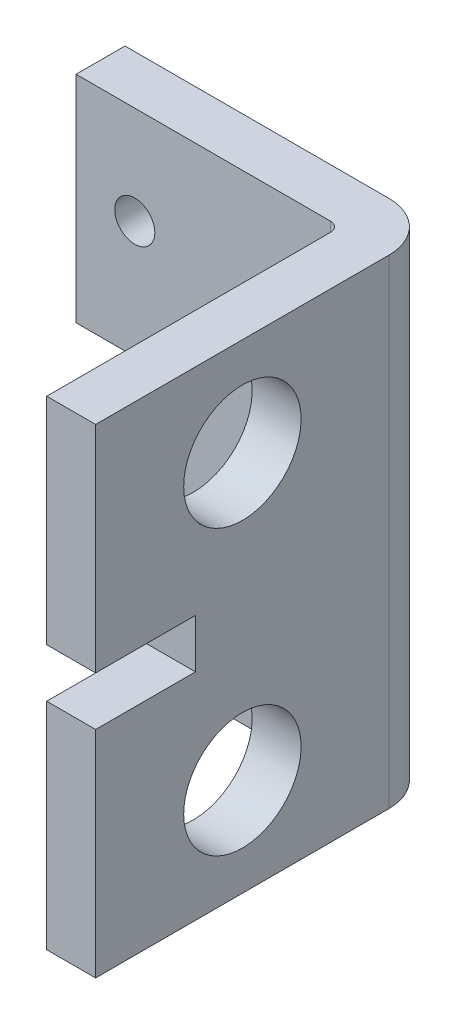
SolidWorks part; units mm, degrees
ref_plane "Front Plane" through (0, 0, 0) normal (0, 0, 1) x (1, 0, 0)
ref_plane "Top Plane" through (0, 0, 0) normal (0, 1, 0) x (1, 0, 0)
ref_plane "Right Plane" through (0, 0, 0) normal (1, 0, 0) x (0, 0, -1)
sketch "Sketch2" plane through (0, 0, 0) normal (0, 0, 1) x (1, 0, 0)
  line L1 (0, 0) -> (27, 0)
  line L2 (0, 0) -> (0, 49)
  line L3 (0, 49) -> (27, 49)
  line L4 (27, 0) -> (27, 49)
  line L5 (6, 39) -> (21, 39) construction
  line L6 (6, 39) -> (6, 10) construction
  line L7 (6, 10) -> (21, 10) construction
  line L8 (21, 39) -> (21, 10) construction
  circle A0 centre (6, 39) radius 2.05
  circle A1 centre (21, 39) radius 2.05
  circle A2 centre (6, 10) radius 2.05
  circle A3 centre (21, 10) radius 2.05
  point P13 (13.5, 10)
  point P14 (13.5, 0)
  point P15 (6, 24.5)
  point P16 (0, 24.5)
  dimension "D1" = 4.1
  dimension "D2" = 15
  dimension "D3" = 29
  dimension "D4" = 10
  dimension "D5" = 6
extrude "Boss-Extrude1" add sketch "Sketch2" along normal blind 5
sketch "Sketch4" plane through (0, 49, 0) normal (0, 1, 0) x (1, 0, 0)
  line L0 (27, 0) -> (0, 0) construction
  line L2 (32, -5) -> (32, -35)
  line L3 (32, -35) -> (27, -35)
  line L5 (27, -5) -> (27, 0) construction
  line L8 (27, -35) -> (27, 0)
  arc A0 (27, 0) -> (32, -5) centre (27, -5) cw
  dimension "D1" = 30
extrude "Boss-Extrude2" add sketch "Sketch4" against normal up to surface (49 mm away) up to face at (13.5, 0, 2.5)
sketch "Sketch5" plane through (27, 0, 0) normal (-1, 0, 0) x (0, 0, 1)
  line L1 (35, 0) -> (5, 0) construction
  line L2 (35, 0) -> (35, 49) construction
  circle A0 centre (20, 39) radius 6
  circle A1 centre (20, 10) radius 6
  point P4 (0, 0)
  point P5 (0, 0)
  dimension "D1" = 12
  dimension "D2" = 29
  dimension "D3" = 10
  dimension "D4" = 15
extrude "Cut-Extrude1" cut sketch "Sketch5" against normal through all
fillet "Fillet1" radius 1 1 edges at (27, 24.5, 5)
sketch "Sketch6" plane through (0, 0, 5) normal (0, 0, 1) x (1, 0, 0)
  line L0 (0, 49) -> (0, 0) construction
  line L1 (-3, 27) -> (10.2, 27)
  line L2 (-3, 27) -> (-3, 22)
  line L3 (-3, 22) -> (10.2, 22)
  line L4 (10.2, 27) -> (10.2, 22)
  point P8 (0, 24.5)
  point P9 (-3, 24.5)
  dimension "D1" = 5
  dimension "D2" = 3
  dimension "D3" = 10.2
extrude "Cut-Extrude2" cut sketch "Sketch6" against normal through all
sketch "Sketch7" plane through (27, 0, 0) normal (-1, 0, 0) x (0, 0, 1)
  line L0 (35, 0) -> (35, 49) construction
  line L1 (35, 27) -> (24.8, 27)
  line L2 (35, 27) -> (35, 22)
  line L3 (35, 22) -> (24.8, 22)
  line L4 (24.8, 27) -> (24.8, 22)
  line L5 (0, 27) -> (5, 27) construction
  line L6 (5, 22) -> (0, 22) construction
  dimension "D1" = 10.2
extrude "Cut-Extrude3" cut sketch "Sketch7" against normal through all and the other way through all
